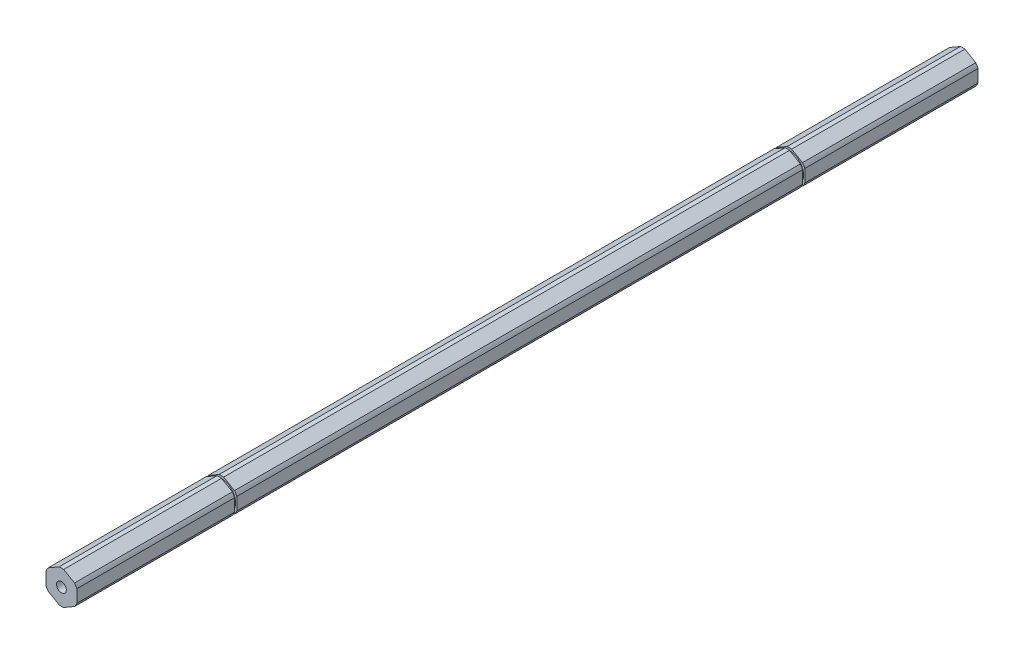
SolidWorks part; units mm, degrees
material "6061-T6 (SS)"
ref_plane "Front Plane" through (0, 0, 0) normal (0, 0, 1) x (1, 0, 0)
ref_plane "Top Plane" through (0, 0, 0) normal (0, 1, 0) x (1, 0, 0)
ref_plane "Right Plane" through (0, 0, 0) normal (1, 0, 0) x (0, 0, -1)
sketch "Sketch1" plane through (0, 0, 0) normal (0, 0, 1) x (1, 0, 0)
  line L1 (0, 7.3323) -> (-6.35, 3.6662)
  line L2 (-6.35, 3.6662) -> (-6.35, -3.6662)
  line L3 (-6.35, -3.6662) -> (0, -7.3323)
  line L4 (0, -7.3323) -> (6.35, -3.6662)
  line L5 (6.35, -3.6662) -> (6.35, 3.6662)
  line L6 (6.35, 3.6662) -> (0, 7.3323)
  circle A0 centre (0, 0) radius 6.35 construction
  circle A1 centre (0, 0) radius 6.858
  dimension "D1" = 12.7
  dimension "D2" = 13.716
extrude "Boss-Extrude1" add sketch "Sketch1" along normal mid plane 371.602 contours L5 A1 L6 L1 L2 L3 L4 region at (0, 0, 0)
sketch "Sketch2" plane through (0, 0, 185.801) normal (0, 0, 1) x (1, 0, 0)
  circle A0 centre (0, 0) radius 2.0193
  dimension "D1" = 4.0386
extrude "Cut-Extrude1" cut sketch "Sketch2" against normal through all
sketch "Sketch4" plane through (0, 0, 0) normal (0, 1, 0) x (1, 0, 0)
  line L0 (-2.0193, -185.801) -> (2.0193, -185.801) construction
  line L5 (-0.9317, -185.801) -> (0.9317, -185.801) construction
  line L7 (9.0297, 114.3762) -> (5.8547, 114.3762)
  line L8 (9.0297, 114.3762) -> (9.0297, 113.4872)
  line L9 (9.0297, 113.4872) -> (5.8547, 113.4872)
  line L10 (5.8547, 114.3762) -> (5.8547, 113.4872)
  line L11 (5.8547, -120.7262) -> (9.0297, -120.7262)
  line L12 (0, 185.801) -> (0, -185.801) construction
  line L13 (2.0193, 185.801) -> (-2.0193, 185.801) construction
  line L14 (5.8547, -120.7262) -> (5.8547, -119.8372)
  line L15 (5.8547, -119.8372) -> (9.0297, -119.8372)
  line L16 (9.0297, -120.7262) -> (9.0297, -119.8372)
  dimension "D1" = 0.889
  dimension "D2" = 371.602
  dimension "D3" = 5.8547
  dimension "D4" = 71.4248
  dimension "D5" = 3.175
  dimension "D6" = 3.175
  dimension "D7" = 0.889
  dimension "D8" = 65.0748
revolve "Cut-Revolve4" cut sketch "Sketch4" angle 360 about L12
equation "\"D1@Boss-Extrude1\"=14.25"
